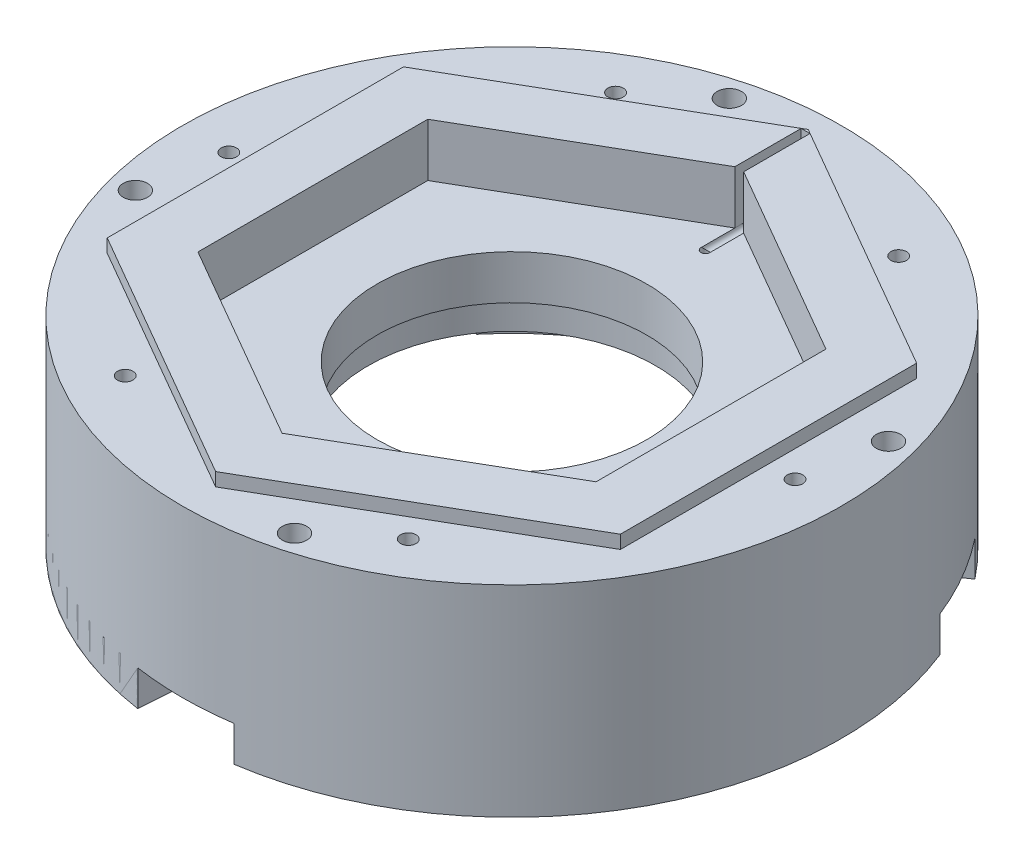
SolidWorks part; units mm, degrees
ref_plane "Alzado" through (0, 0, 0) normal (0, 0, 1) x (1, 0, 0)
ref_plane "Planta" through (0, 0, 0) normal (0, 1, 0) x (1, 0, 0)
ref_plane "Vista lateral" through (0, 0, 0) normal (1, 0, 0) x (0, 0, -1)
sketch "Croquis1" plane through (0, 0, 0) normal (0, 1, 0) x (1, 0, 0)
  circle A0 centre (0, 0) radius 38.85
  circle A1 centre (0, 0) radius 32.5
  dimension "D1" = 77.7
  dimension "D2" = 65
extrude "Saliente-Extruir1" add sketch "Croquis1" along normal blind 17
sketch "Croquis3" plane through (0, 17, 0) normal (0, 1, 0) x (1, 0, 0)
  circle A0 centre (0, 0) radius 59.5
  circle A1 centre (0, 0) radius 38.85
  circle A2 centre (0, 0) radius 38.85 construction
  dimension "D1" = 119
extrude "Saliente-Extruir2" add sketch "Croquis3" against normal blind 5 separate body
sketch "Croquis4" plane through (0, 17, 0) normal (0, 1, 0) x (1, 0, 0)
  circle A0 centre (0, 0) radius 59.5
  circle A1 centre (0, 0) radius 74.5
  circle A2 centre (0, 0) radius 59.5 construction
  dimension "D1" = 15
extrude "Saliente-Extruir3" add sketch "Croquis4" against normal blind 28.5
sketch "Croquis5" plane through (0, 17, 0) normal (0, 1, 0) x (1, 0, 0)
  line L1 (0, 51.9615) -> (-45, 25.9808)
  line L2 (-45, 25.9808) -> (-45, -25.9808)
  line L3 (-45, -25.9808) -> (0, -51.9615)
  line L4 (0, -51.9615) -> (45, -25.9808)
  line L5 (45, -25.9808) -> (45, 25.9808)
  line L6 (45, 25.9808) -> (0, 51.9615)
  circle A2 centre (0, 0) radius 74.5
  circle A3 centre (0, 0) radius 74.5 construction
  circle A5 centre (0, 0) radius 45 construction
  dimension "D1" = 90
extrude "Saliente-Extruir4" add sketch "Croquis5" along normal blind 12
sketch "Croquis6" plane through (0, 17, 0) normal (0, 1, 0) x (1, 0, 0)
  circle A0 centre (0, 0) radius 32.5
  circle A1 centre (0, 0) radius 32.5 construction
  circle A2 centre (0, 0) radius 30.5
  dimension "D1" = 2
extrude "Saliente-Extruir5" add sketch "Croquis6" against normal blind 10 separate body
sketch "Croquis9" plane through (0, 12, 0) normal (0, -1, 0) x (-1, 0, 0)
  circle A0 centre (0, 0) radius 38.85
  circle A1 centre (0, 0) radius 40.85
  circle A2 centre (0, 0) radius 38.85 construction
  dimension "D1" = 2
extrude "Saliente-Extruir6" add sketch "Croquis9" along normal blind 1
sketch "Croquis10" plane through (0, 0, 0) normal (0, -1, 0) x (1, 0, 0)
  line L0 (0, 0) -> (0, 93.1519)
  line L1 (0, 0) -> (0, -93.1519)
  arc A0 (0, 93.1519) -> (0, -93.1519) centre (0, 0) ccw
extrude "Cortar-Extruir1" cut sketch "Croquis10" against normal through all both and the other way through all
sketch "Croquis17" plane through (0, -11.5, 0) normal (0, -1, 0) x (-1, 0, 0)
  line L6 (55.7371, 20.8237) -> (69.2656, 27.4321)
  line L7 (45.9024, 37.8579) -> (58.3897, 46.2697)
  line L8 (-45.9024, 37.8579) -> (-58.3897, 46.2697)
  line L9 (-55.7371, 20.8237) -> (-69.2577, 27.4522)
  line L10 (-9.8347, -58.6816) -> (-10.8759, -73.7019)
  line L11 (9.8347, -58.6816) -> (10.8759, -73.7019)
  arc A0 (58.3897, 46.2697) -> (-58.3897, 46.2697) centre (0, 0) ccw
  arc A1 (45.9024, 37.8579) -> (-45.9024, 37.8579) centre (0, 0) ccw
  arc A2 (10.8759, -73.7019) -> (69.2656, 27.4321) centre (0, 0) ccw
  arc A3 (9.8347, -58.6816) -> (55.7371, 20.8237) centre (0, 0) ccw
  arc A4 (-55.7371, 20.8237) -> (-9.8347, -58.6816) centre (0, 0) ccw
  arc A5 (-69.2577, 27.4522) -> (-10.8759, -73.7019) centre (0, 0) ccw
  arc A6 (0, 59.5) -> (0, -59.5) centre (0, 0) ccw construction
  arc A7 (0, 74.5) -> (0, -74.5) centre (0, 0) ccw construction
  point P19 (0, 0)
extrude "Saliente-Extruir7" add sketch "Croquis17" along normal blind 8
sketch "Croquis11" plane through (0, 0, 0) normal (-1, 0, 0) x (0, 0, 1)
  line L0 (-43.85, 12) -> (-43.85, 17)
  line L1 (-59.5, 12) -> (59.5, 12) construction
  line L2 (-43.85, 17) -> (-71.5, 17)
  line L3 (-71.5, 17) -> (-71.5, -19.5)
  line L5 (-74.5, 29) -> (-74.5, -11.5) construction
  line L6 (-30.5, 17) -> (-51.9615, 17) construction
  line L7 (-40.85, 11) -> (-40.85, 12) construction
  line L10 (-74.5, -19.5) -> (-46.2697, -19.5) construction
  dimension "D1" = 3
  dimension "D2" = 0
  dimension "D3" = 3
sketch "Croquis12" plane through (0, 12, 0) normal (0, -1, 0) x (-1, 0, 0)
  line L0 (0, 40.85) -> (0, 59.5) construction
  circle A0 centre (0, 43.7498) radius 1
  dimension "D1" = 2
sweep "Cortar-Barrer1" cut profiles "Croquis12" path "Croquis11"
mirror "Simetría2" about plane through (0, 29, 0) normal (1, 0, 0) of bodies 118
sketch "Croquis14" plane through (0, -11.5, 0) normal (0, -1, 0) x (1, 0, 0)
  circle A0 centre (0, 69) radius 1.75
  circle A1 centre (59.7558, -34.5) radius 1.75
  circle A2 centre (-59.7558, -34.5) radius 1.75
  point P10 (0, 0)
  dimension "D1" = 3.5
  dimension "D2" = 69
  dimension "D3" = 3
extrude "Cortar-Extruir2" cut sketch "Croquis14" against normal blind 5
sketch "Croquis15" plane through (0, 29, 0) normal (0, 1, 0) x (1, 0, 0)
  line L1 (-58, -33.4863) -> (0, -66.9726)
  line L2 (0, -66.9726) -> (58, -33.4863)
  line L3 (58, -33.4863) -> (58, 33.4863)
  line L4 (58, 33.4863) -> (0, 66.9726)
  line L5 (0, 66.9726) -> (-58, 33.4863)
  line L6 (-58, 33.4863) -> (-58, -33.4863)
  circle A0 centre (0, 0) radius 58 construction
  circle A1 centre (0, 0) radius 74.5 construction
  circle A2 centre (0, 0) radius 74.5
  circle A3 centre (0, 0) radius 32
  circle M7 centre (0, 0) radius 74.5
  dimension "D1" = 64
  dimension "D2" = 116
extrude "Cortar-Extruir4" cut sketch "Croquis15" against normal blind 3 contours L3 M7 | L4 M7 | L2 M7 | L1 M7 | L6 M7 | L5 M7 region at (-72.3928, 29, 0)
sketch "Croquis16" plane through (0, 26, 0) normal (0, 1, 0) x (1, 0, 0)
  circle A0 centre (-64, 0) radius 1.75
  circle A1 centre (-32, 55.4256) radius 1.75
  circle A2 centre (32, 55.4256) radius 1.75
  circle A3 centre (64, 0) radius 1.75
  circle A4 centre (32, -55.4256) radius 1.75
  circle A5 centre (-32, -55.4256) radius 1.75
  dimension "D1" = 3.5
  dimension "D2" = 64
  dimension "D3" = 6
extrude "Cortar-Extruir5" cut sketch "Croquis16" against normal blind 5
sketch "Croquis18" plane through (0, -19.5, 0) normal (0, -1, 0) x (-1, 0, 0)
  line L0 (0, 0) -> (0, -69) construction
  line L1 (0, 0) -> (51.8655, -89.8337) construction
  circle A0 centre (34.5, -59.7558) radius 1.75
  circle A2 centre (-69, 0) radius 1.75
  circle A3 centre (34.5, 59.7558) radius 1.75
  point P14 (0, 0)
  dimension "D1" = 3.5
  dimension "D3" = 69
  dimension "D2" = 30
  dimension "D4" = 3
extrude "Cortar-Extruir6" cut sketch "Croquis18" against normal blind 5
sketch "Croquis19" plane through (0, 29, 0) normal (0, 1, 0) x (1, 0, 0)
  line L0 (-1, 51.3842) -> (-1, 66.3842)
  line L1 (-1, 66.3842) -> (0.995, 66.3842)
  line L2 (0.995, 66.3842) -> (0.995, 51.3842)
  line L3 (0.995, 51.3871) -> (0.995, 43.85) construction
  line L4 (0.995, 51.3842) -> (-1, 51.3842)
  dimension "D1" = 15
extrude "Cortar-Extruir7" cut sketch "Croquis19" against normal up to surface (12 mm away) up to face at (0, 17, -15.268)
sketch "Croquis21" plane through (0, -19.5, 0) normal (0, -1, 0) x (1, 0, 0)
  circle A0 centre (-34.5, 59.7558) radius 1.5
  arc A2 (-10.8759, 73.7019) -> (-69.2577, -27.4522) centre (0, 0) ccw construction
  dimension "D1" = 3
  dimension "D2" = 69
extrude "Cortar-Extruir8" cut sketch "Croquis21" against normal blind 5
sketch "Croquis22" plane through (0, -19.5, 0) normal (0, -1, 0) x (1, 0, 0)
  line L0 (0, 0) -> (0, 83.9904) construction
  line L1 (0, 0) -> (23.3364, 87.0928) construction
  circle A0 centre (17.9879, 67.1318) radius 2.75
  circle A2 centre (67.1318, -17.9879) radius 2.75
  circle A3 centre (-17.9879, -67.1318) radius 2.75
  circle A4 centre (-67.1318, 17.9879) radius 2.75
  arc A5 (69.2577, -27.4522) -> (10.8759, 73.7019) centre (0, 0) ccw construction
  point P20 (0, 0)
  dimension "D1" = 5.5
  dimension "D2" = 69.5
  dimension "D3" = 15
  dimension "D4" = 4
extrude "Cortar-Extruir9" cut sketch "Croquis22" against normal through all
sketch "Sketch1" plane through (0, -19.5, 0) normal (0, -1, 0) x (-1, 0, 0)
  line L0 (0, 0) -> (-58.3897, 46.2697) construction
  line L1 (0, 0) -> (-43.5151, 85.2719) construction
  circle A2 centre (-28.1022, 55.069) radius 1.5
  circle A3 centre (28.1022, -55.069) radius 1.5
  point P12 (0, 0)
  dimension "D1" = 3
  dimension "D2" = 24.57
  dimension "D3" = 61.825
  dimension "D4" = 2
extrude "Cut-Extrude1" cut sketch "Sketch1" against normal blind 5
equation "\"ºº5\"=110"
